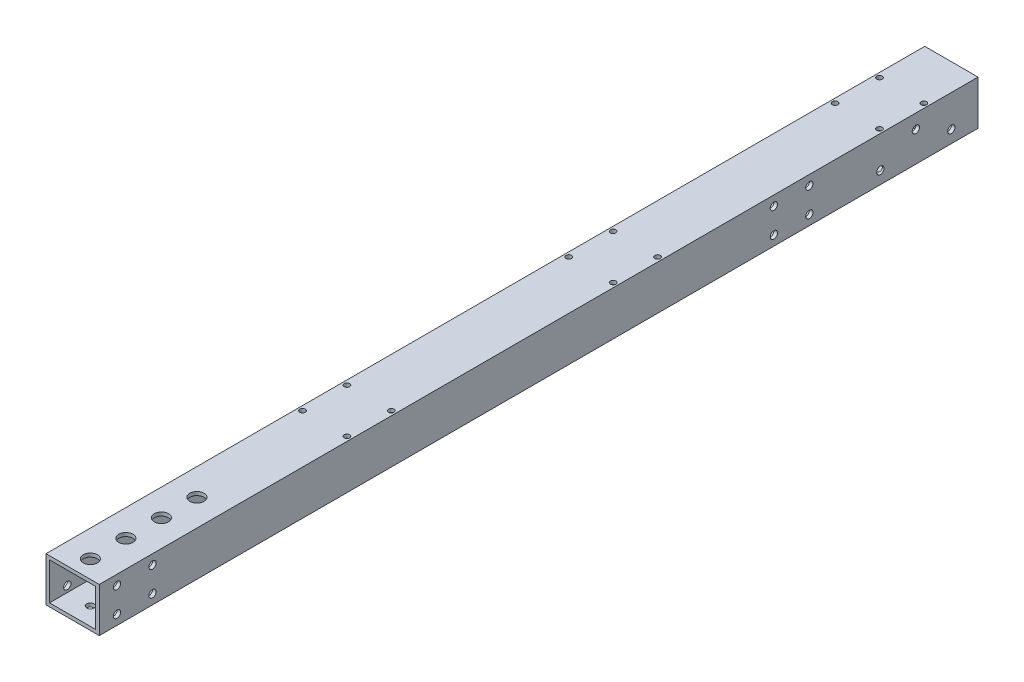
SolidWorks part; units mm, degrees
material "6063-T1"
ref_plane "前视基准面" through (0, 0, 0) normal (0, 0, 1) x (1, 0, 0)
ref_plane "上视基准面" through (0, 0, 0) normal (0, 1, 0) x (1, 0, 0)
ref_plane "右视基准面" through (0, 0, 0) normal (1, 0, 0) x (0, 0, -1)
other "Configuration Table"
sketch "草图1" plane through (0, 0, 0) normal (0, 0, 1) x (1, 0, 0)
  line L1 (-15, 12.5) -> (15, 12.5)
  line L2 (-15, 12.5) -> (-15, -12.5)
  line L3 (-15, -12.5) -> (15, -12.5)
  line L4 (15, 12.5) -> (15, -12.5)
  line L7 (-13, 10.5) -> (13, 10.5)
  line L8 (-13, 10.5) -> (-13, -10.5)
  line L9 (-13, -10.5) -> (13, -10.5)
  line L10 (13, 10.5) -> (13, -10.5)
  line L11 (-13, 10.5) -> (13, -10.5) construction
  line L12 (-13, -10.5) -> (13, 10.5) construction
  point P0 (0, 0)
  point P6 (0, 0)
  dimension "D1" = 30
  dimension "D2" = 25
  dimension "D3" = 2
  dimension "D4" = 2
  dimension "D5" = 2
  dimension "D6" = 2
extrude "凸台-拉伸1" add sketch "草图1" along normal blind 510
sketch "草图4" plane through (0, -12.5, 0) normal (0, -1, 0) x (1, 0, 0)
  line L0 (0, 40) -> (0, 60) construction
  line L1 (-7.5, 40) -> (-7.5, 60)
  line L2 (7.5, 40) -> (7.5, 60)
  line L3 (-15, 0) -> (15, 0) construction
  line L4 (0, 190) -> (0, 210) construction
  line L5 (-7.5, 190) -> (-7.5, 210)
  line L6 (7.5, 190) -> (7.5, 210)
  line L7 (0, 340) -> (0, 360) construction
  line L8 (-7.5, 340) -> (-7.5, 360)
  line L9 (7.5, 340) -> (7.5, 360)
  line L10 (0, 40) -> (0, 190) construction
  arc A0 (-7.5, 40) -> (7.5, 40) centre (0, 40) ccw
  arc A1 (7.5, 60) -> (-7.5, 60) centre (0, 60) ccw
  arc A2 (-7.5, 190) -> (7.5, 190) centre (0, 190) ccw
  arc A3 (7.5, 210) -> (-7.5, 210) centre (0, 210) ccw
  arc A4 (-7.5, 340) -> (7.5, 340) centre (0, 340) ccw
  arc A5 (7.5, 360) -> (-7.5, 360) centre (0, 360) ccw
  point P3 (0, 50)
  point P14 (0, 200)
  point P21 (0, 350)
  dimension "D1" = 40
  dimension "D2" = 15
  dimension "D3" = 20
  dimension "D5" = 150
  dimension "D4" = 3
extrude "切除-拉伸4" cut sketch "草图4" against normal up to next
sketch "草图5" plane through (0, 12.5, 0) normal (0, 1, 0) x (1, 0, 0)
  line L0 (15, 0) -> (-15, 0) construction
  line L5 (0, 0) -> (0, -20.1517) construction
  circle A0 centre (-12.5, -43) radius 1.55
  circle A1 centre (12.5, -43) radius 1.55
  circle A2 centre (-12.5, -68) radius 1.55
  circle A3 centre (12.5, -68) radius 1.55
  circle A4 centre (-12.5, -193) radius 1.55
  circle A5 centre (-12.5, -218) radius 1.55
  circle A6 centre (12.5, -193) radius 1.55
  circle A7 centre (12.5, -218) radius 1.55
  circle A8 centre (-12.5, -343) radius 1.55
  circle A9 centre (-12.5, -368) radius 1.55
  circle A10 centre (12.5, -343) radius 1.55
  circle A11 centre (12.5, -368) radius 1.55
  dimension "D1" = 3.1
  dimension "D6" = 150
  dimension "D7" = 150
  dimension "D2" = 25
  dimension "D3" = 25
  dimension "D4" = 43
  dimension "D5" = 3
sketch "草图7" plane through (15, 0, 0) normal (1, 0, 0) x (0, 0, -1)
  line L0 (0, -12.5) -> (0, 12.5) construction
  line L2 (-510, -12.5) -> (0, -12.5) construction
  line L3 (-510, 12.5) -> (0, 12.5) construction
  circle A0 centre (-30, -5.5) radius 2.05
  circle A1 centre (-50, 4.5) radius 2.05
  circle A2 centre (-70, -5.5) radius 2.05
  dimension "D1" = 4.1
  dimension "D2" = 30
  dimension "D3" = 7
  dimension "D4" = 8
  dimension "D5" = 20
  dimension "D6" = 20
extrude "切除-拉伸7" cut sketch "草图7" against normal through all
sketch "草图9" plane through (0, -12.5, 0) normal (0, -1, 0) x (1, 0, 0)
  line L1 (0, 430) -> (9.292, 430) construction
  line L2 (0, 470) -> (9.6668, 470) construction
  circle A0 centre (0, 480) radius 2.05
  circle A1 centre (0, 500) radius 2.05
  circle A2 centre (0, 440) radius 2.05
  circle A3 centre (0, 460) radius 2.05
  dimension "D1" = 20
  dimension "D2" = 4.1
extrude "切除-拉伸9" cut sketch "草图9" against normal blind 10
sketch "草图10" plane through (0, 12.5, 0) normal (0, 1, 0) x (1, 0, 0)
  line L2 (0, -470) -> (-5.6573, -470) construction
  line L3 (0, -430) -> (-6.775, -430) construction
  circle A0 centre (0, -500) radius 4
  circle A1 centre (0, -480) radius 4
  circle A2 centre (0, -460) radius 4
  circle A3 centre (0, -440) radius 4
  dimension "D1" = 8
  dimension "D2" = 20
extrude "切除-拉伸10" cut sketch "草图10" against normal blind 10
sketch "草图11" plane through (-15, 0, 0) normal (-1, 0, 0) x (0, 0, 1)
  line L0 (0, 0) -> (27.3376, 0) construction
  line L1 (0, 12.5) -> (0, -12.5) construction
  line L2 (510, 0) -> (502.3475, 0) construction
  line L3 (510, 12.5) -> (510, -12.5) construction
  circle A0 centre (480, 7) radius 2.05
  circle A1 centre (500, 7) radius 2.05
  circle A2 centre (480, -7) radius 2.05
  circle A3 centre (500, -7) radius 2.05
  circle A4 centre (110, 7) radius 2.05
  circle A5 centre (130, 7) radius 2.05
  circle A6 centre (110, -7) radius 2.05
  circle A7 centre (130, -7) radius 2.05
  dimension "D1" = 4.1
  dimension "D2" = 14
  dimension "D4" = 110
  dimension "D5" = 4.1
  dimension "D7" = 14
  dimension "D8" = 10
  dimension "D3" = 20
  dimension "D6" = 20
extrude "切除-拉伸11" cut sketch "草图11" against normal blind 52
sketch "草图12" plane through (-15, 0, 0) normal (-1, 0, 0) x (0, 0, 1)
  line L0 (510, -12.5) -> (0, -12.5) construction
  line L1 (0, 12.5) -> (15, 12.5)
  line L2 (0, 12.5) -> (0, -12.5)
  line L3 (0, -12.5) -> (15, -12.5)
  line L4 (15, 12.5) -> (15, -12.5)
  dimension "D1" = 15
extrude "切除-拉伸12" cut sketch "草图12" against normal through all
extrude "切除-拉伸13" cut sketch "草图5" against normal up to next
